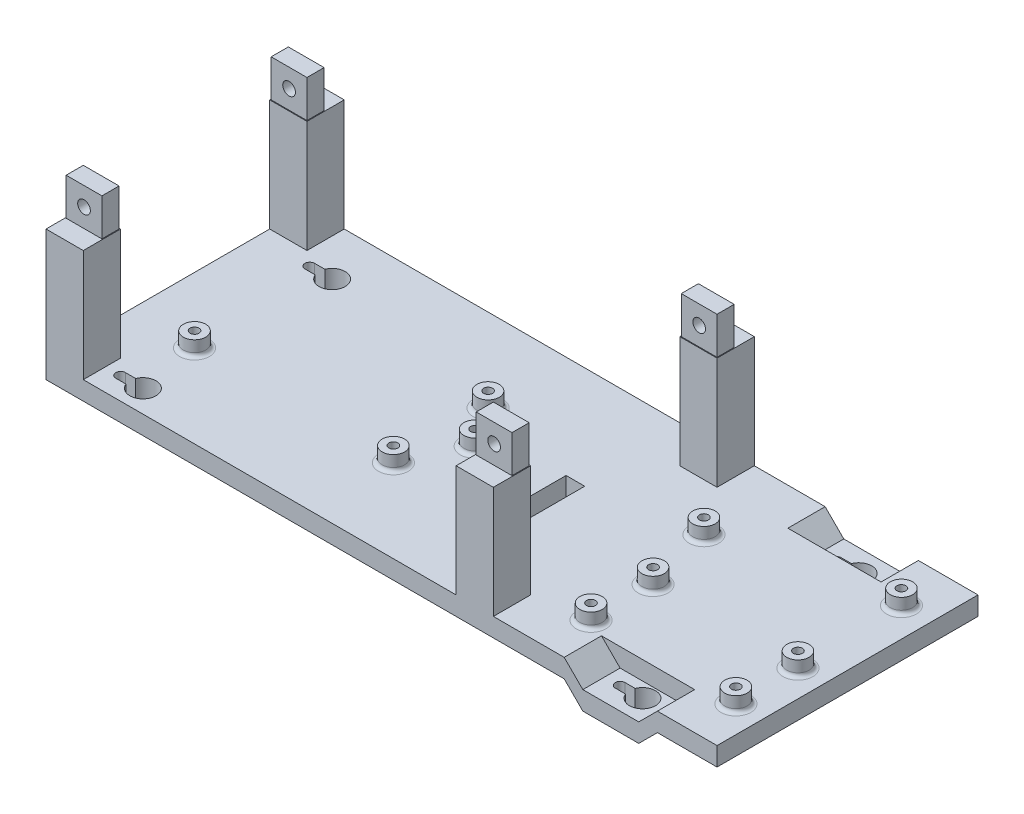
SolidWorks part; units mm, degrees
ref_plane "Front Plane" through (0, 0, 0) normal (0, 0, 1) x (1, 0, 0)
ref_plane "Top Plane" through (0, 0, 0) normal (0, 1, 0) x (1, 0, 0)
ref_plane "Right Plane" through (0, 0, 0) normal (1, 0, 0) x (0, 0, -1)
sketch "Sketch1" plane through (0, 0, 0) normal (0, 1, 0) x (1, 0, 0)
  line L1 (-90, -35) -> (90, -35)
  line L2 (-90, -35) -> (-90, 35)
  line L3 (-90, 35) -> (90, 35)
  line L4 (90, -35) -> (90, 35)
  line L5 (-90, -35) -> (90, 35) construction
  line L6 (-90, 35) -> (90, -35) construction
  point P0 (0, 0)
  dimension "D1" = 180
  dimension "D2" = 70
extrude "Boss-Extrude1" add sketch "Sketch1" along normal blind 5
sketch "Sketch3" plane through (0, 5, 0) normal (0, 1, 0) x (1, 0, 0)
  line L0 (90, 35) -> (-90, 35) construction
  line L1 (69, 35) -> (54, 35)
  line L2 (69, 35) -> (69, 25)
  line L3 (69, 25) -> (54, 25)
  line L4 (54, 35) -> (54, 25)
  line L5 (-90, -35) -> (90, -35) construction
  line L6 (69, -35) -> (54, -35)
  line L7 (69, -35) -> (69, -25)
  line L8 (69, -25) -> (54, -25)
  line L9 (54, -35) -> (54, -25)
  line L10 (90, -35) -> (90, 35) construction
  dimension "D1" = 10
  dimension "D2" = 15
  dimension "D3" = 21
extrude "Cut-Extrude1" cut sketch "Sketch3" against normal blind 6
chamfer "Chamfer2" distance 5 angle 45 4 edges at (54, 5, 30) (69, 5, 30) (69, 5, -30) (54, 5, -30)
sketch "Sketch5" plane through (0, 0, 0) normal (0, -1, 0) x (1, 0, 0)
  line L0 (-90, 35) -> (54, 35) construction
  line L1 (49, 35) -> (74, 35)
  line L2 (49, 35) -> (49, 23)
  line L3 (49, 23) -> (74, 23)
  line L4 (74, 35) -> (74, 23)
  line L5 (54, -35) -> (-90, -35) construction
  line L6 (49, -35) -> (74, -35)
  line L7 (49, -35) -> (49, -23)
  line L8 (49, -23) -> (74, -23)
  line L9 (74, -35) -> (74, -23)
  line L10 (74, 25) -> (74, 35) construction
  line L11 (49, 35) -> (49, 25) construction
  dimension "D1" = 12
extrude "Boss-Extrude7" add sketch "Sketch5" along normal blind 5
chamfer "Chamfer4" distance 5 angle 45 4 edges at (49, -5, 29) (74, -5, 29) (74, -5, -29) (49, -5, -29)
sketch "Sketch6" plane through (0, 0, 0) normal (0, 1, 0) x (1, 0, 0)
  line L0 (58, -29) -> (64, -29) construction
  line L1 (58, -27.7) -> (64, -27.7)
  line L2 (58, -30.3) -> (64, -30.3)
  line L3 (69, -35) -> (54, -35) construction
  line L5 (58, 29) -> (64, 29) construction
  line L6 (58, 30.3) -> (64, 30.3)
  line L7 (58, 27.7) -> (64, 27.7)
  line L8 (54, 35) -> (69, 35) construction
  line L9 (69, -25) -> (69, -35) construction
  circle A0 centre (64, -29) radius 3.5
  arc A1 (58, -27.7) -> (58, -30.3) centre (58, -29) ccw
  arc A2 (64, -30.3) -> (64, -27.7) centre (64, -29) ccw
  circle A3 centre (64, 29) radius 3.5
  arc A4 (58, 30.3) -> (58, 27.7) centre (58, 29) ccw
  arc A5 (64, 27.7) -> (64, 30.3) centre (64, 29) ccw
  point P2 (61, -29)
  point P15 (61, 29)
  dimension "D1" = 7
  dimension "D2" = 2.6
  dimension "D3" = 6
  dimension "D4" = 5
  dimension "D5" = 6
  dimension "D6" = 6
extrude "Cut-Extrude2" cut sketch "Sketch6" against normal through all contours A4 L6 A0 L7 | L6 A4 L7 A0 | L7 A5 L6 A0 | L1 A1 L2 | L2 A2 L1 | A2 L2 A0 L1 region at (58.7697, 0, 29) region at (64.6436, 0, 25.6587) region at (62.8105, 0, 29) region at (58.7697, 0, -29) region at (64.6436, 0, -32.3413) region at (62.8105, 0, -29)
sketch "Sketch7" plane through (0, 5, 0) normal (0, 1, 0) x (1, 0, 0)
  line L0 (-76, -29) -> (-70, -29) construction
  line L1 (-76, -27.7) -> (-70, -27.7)
  line L2 (-76, -30.3) -> (-70, -30.3)
  line L4 (-90, -35) -> (49, -35) construction
  line L5 (-90, 35) -> (-90, -35) construction
  line L6 (-76, 21.75) -> (-70, 21.75) construction
  line L7 (-76, 23.05) -> (-70, 23.05)
  line L8 (-76, 20.45) -> (-70, 20.45)
  circle A0 centre (-70, -29) radius 3.5
  arc A1 (-76, -27.7) -> (-76, -30.3) centre (-76, -29) ccw
  arc A2 (-70, -30.3) -> (-70, -27.7) centre (-70, -29) ccw
  circle A3 centre (-70, 21.75) radius 3.5
  arc A4 (-76, 23.05) -> (-76, 20.45) centre (-76, 21.75) ccw
  arc A5 (-70, 20.45) -> (-70, 23.05) centre (-70, 21.75) ccw
  point P3 (-73, -29)
  point P14 (-73, 21.75)
  dimension "D3" = 7
  dimension "D6" = 50.75
  dimension "D1" = 6
  dimension "D2" = 2.6
  dimension "D4" = 6
  dimension "D5" = 20
extrude "Cut-Extrude3" cut sketch "Sketch7" against normal through all contours A2 L2 A0 L1 | A5 L8 A3 L7 | L1 A2 L2 A1 | L8 A5 L7 A4 region at (-69.3564, 5, 25.6587) region at (-69.3564, 5, -25.0913)
sketch "Sketch8" plane through (0, 5, 0) normal (0, 1, 0) x (1, 0, 0)
  line L1 (-90, -35) -> (-80, -35)
  line L2 (-90, -35) -> (-90, -25)
  line L3 (-90, -25) -> (-80, -25)
  line L4 (-80, -35) -> (-80, -25)
  line L5 (-90, 35) -> (-80, 35)
  line L6 (-90, 35) -> (-90, 25)
  line L7 (-90, 25) -> (-80, 25)
  line L8 (-80, 35) -> (-80, 25)
  line L9 (30, -35) -> (20, -35)
  line L10 (30, -35) -> (30, -25)
  line L11 (30, -25) -> (20, -25)
  line L12 (20, -35) -> (20, -25)
  line L13 (30, 35) -> (20, 35)
  line L14 (30, 35) -> (30, 25)
  line L15 (30, 25) -> (20, 25)
  line L16 (20, 35) -> (20, 25)
  dimension "D1" = 10
  dimension "D2" = 10
  dimension "D3" = 120
extrude "Boss-Extrude8" add sketch "Sketch8" along normal blind 40
sketch "Sketch9" plane through (0, 45, 0) normal (0, 1, 0) x (1, 0, 0)
  line L1 (20, 35) -> (20, 25) construction
  line L2 (30, 35) -> (20, 35)
  line L3 (30, 35) -> (30, 30)
  line L4 (30, 30) -> (20, 30)
  line L5 (20, 35) -> (20, 30)
  line L6 (-90, 35) -> (-90, 25) construction
  line L8 (-80, 35) -> (-90, 35)
  line L9 (-80, 35) -> (-80, 30)
  line L10 (-80, 30) -> (-90, 30)
  line L11 (-90, 35) -> (-90, 30)
  line L12 (-90, -25) -> (-90, -35) construction
  line L14 (-80, -35) -> (-90, -35)
  line L15 (-80, -35) -> (-80, -30)
  line L16 (-80, -30) -> (-90, -30)
  line L17 (-90, -35) -> (-90, -30)
  line L18 (20, -25) -> (20, -35) construction
  line L20 (30, -35) -> (20, -35)
  line L21 (30, -35) -> (30, -30)
  line L22 (30, -30) -> (20, -30)
  line L23 (20, -35) -> (20, -30)
  line L57 (-90, 30) -> (-89.9, 30)
  line M1 (30, 25) -> (30, 35)
  line M2 (30, 35) -> (20, 35)
  line M3 (20, 35) -> (20, 25)
extrude "Cut-Extrude4" cut sketch "Sketch9" against normal blind 10 contours L10 | L10 | L22 | L22 | L16 | L16 | L23 L20 L21 L22 | L4 M1 M2 M3 | L8 L11 L10 L9 | L17 L14 L15 L16 region at (25, 45, -32.5) region at (-85, 45, -32.5) region at (-85, 45, 32.5) region at (25, 45, 32.5)
hole_wizard "M3 Clearance Hole2" positions "Sketch13" profile "Sketch12" hole size "M3" standard "ANSI Metric" end condition through all
sketch "Sketch13" plane through (0, 0, -35) normal (0, 0, -1) x (-1, 0, 0)
  line L0 (-20, 35) -> (-20, 5) construction
  line L1 (-30, 45) -> (-20, 45) construction
  line L2 (80, 35) -> (80, 5) construction
  point P0 (-25, 40)
  point P2 (85, 40)
  dimension "D1" = 5
  dimension "D2" = 5
  dimension "D3" = 5
sketch "Sketch12" plane through (25, 40, -35) normal (1, 0, 0) x (0, 1, 0)
  line L0 (0, 0) -> (0, 70.0001)
  line L1 (0, 70.0001) -> (1.7, 70.0001)
  line L2 (1.7, 70.0001) -> (1.7, 0)
  line L5 (1.7, 0) -> (0, 0)
  line L11 (0, -6.35) -> (0, 107.95) construction
  dimension "Thru Hole Dia." = 3.4
  dimension "Thru Hole Depth" = 70.0001
hole_wizard "M2 Clearance Hole1" positions "Sketch15" profile "Sketch14" hole size "M2" standard "ANSI Metric"
sketch "Sketch15" plane through (0, 5, 0) normal (0, 1, 0) x (1, 0, 0)
  circle A0 centre (-11.9765, 2.0955) radius 1.0414 construction
  circle A1 centre (4.5335, -12.5095) radius 1.0414 construction
  circle A2 centre (43.979, -22.7775) radius 1.0922 construction
  circle A3 centre (43.979, -6.1405) radius 1.0922 construction
  circle A4 centre (82.841, -22.7775) radius 1.0922 construction
  circle A5 centre (82.841, -6.1405) radius 1.0922 construction
  circle A7 centre (39.235, 12.25) radius 1.0922 construction
  point P0 (43.979, -22.7775)
  point P2 (43.979, -6.1405)
  point P4 (82.841, -6.1405)
  point P6 (82.841, -22.7775)
  point P8 (82.1869, 22.2793)
  point P10 (39.235, 12.25)
  point P12 (4.5335, -12.5095)
  point P14 (-11.9765, 2.0955)
sketch "Sketch14" plane through (43.979, 5, 22.7775) normal (1, 0, 0) x (0, 0, 1)
  line L0 (0, 0) -> (0, 65.741)
  line L1 (0, 65.741) -> (1.2, 65.02)
  line L2 (1.2, 65.02) -> (1.2, 0)
  line L5 (1.2, 0) -> (0, 0)
  line L10 (0, 65.741) -> (-1.2, 65.02) construction
  line L11 (0, -6.35) -> (0, 107.95) construction
  dimension "Hole Dia." = 2.4
  dimension "Hole Depth" = 65.02
  dimension "Drill Angle" = 118
sketch "Sketch16" plane through (0, 45, 0) normal (0, 1, 0) x (1, 0, 0)
  line L18 (20.2, 29.8) -> (20.2, 25.2)
  line L19 (29.8, 29.8) -> (20.2, 29.8)
  line L20 (20.2, 25.2) -> (29.8, 25.2)
  line L21 (29.8, 25.2) -> (29.8, 29.8)
  line L22 (20.2, 29.8) -> (20.2, 25.2)
  line L23 (29.8, 29.8) -> (20.2, 29.8)
  line L24 (20.2, 25.2) -> (29.8, 25.2)
  line L25 (29.8, 25.2) -> (29.8, 29.8)
  line L46 (-80.2, 29.8) -> (-89.8, 29.8)
  line L47 (-89.8, 29.8) -> (-89.8, 25.2)
  line L48 (-89.8, 25.2) -> (-80.2, 25.2)
  line L49 (-80.2, 25.2) -> (-80.2, 29.8)
  line L50 (-80.2, 29.8) -> (-89.8, 29.8)
  line L51 (-89.8, 29.8) -> (-89.8, 25.2)
  line L52 (-89.8, 25.2) -> (-80.2, 25.2)
  line L53 (-80.2, 25.2) -> (-80.2, 29.8)
  line L64 (-80.2, -25.2) -> (-89.8, -25.2)
  line L65 (-89.8, -25.2) -> (-89.8, -29.8)
  line L66 (-89.8, -29.8) -> (-80.2, -29.8)
  line L67 (-80.2, -29.8) -> (-80.2, -25.2)
  line L68 (-80.2, -25.2) -> (-89.8, -25.2)
  line L69 (-89.8, -25.2) -> (-89.8, -29.8)
  line L70 (-89.8, -29.8) -> (-80.2, -29.8)
  line L71 (-80.2, -29.8) -> (-80.2, -25.2)
  line L117 (20.2, -25.2) -> (20.2, -29.8)
  line L118 (20.2, -29.8) -> (29.8, -29.8)
  line L119 (29.8, -29.8) -> (29.8, -25.2)
  line L120 (29.8, -25.2) -> (20.2, -25.2)
  line L121 (20.2, -25.2) -> (20.2, -29.8)
  line L122 (20.2, -29.8) -> (29.8, -29.8)
  line L123 (29.8, -29.8) -> (29.8, -25.2)
  line L124 (29.8, -25.2) -> (20.2, -25.2)
  dimension "D1" = 0.2
  dimension "D2" = 0.2
  dimension "D3" = 0.2
  dimension "D4" = 0.2
extrude "Cut-Extrude5" cut sketch "Sketch16" against normal blind 10 flip side to cut
hole_wizard "M2 Clearance Hole2" positions "Sketch21" profile "Sketch20" hole size "M2" standard "ANSI Metric" end condition through all
sketch "Sketch21" plane through (0, 5, 0) normal (0, 1, 0) x (1, 0, 0)
  circle A0 centre (-19.12, -12.7) radius 1.0922 construction
  circle A1 centre (-19.12, 12.7) radius 1.0922 construction
  circle A2 centre (-72.46, -12.7) radius 1.0922 construction
  point P0 (-19.12, 12.7)
  point P2 (-19.12, -12.7)
  point P4 (-72.46, -12.7)
sketch "Sketch20" plane through (-19.12, 5, -12.7) normal (1, 0, 0) x (0, 0, 1)
  line L0 (0, 0) -> (0, 10)
  line L1 (0, 10) -> (1.2, 10)
  line L2 (1.2, 10) -> (1.2, 0)
  line L5 (1.2, 0) -> (0, 0)
  line L11 (0, -6.35) -> (0, 107.95) construction
  dimension "Thru Hole Dia." = 2.4
  dimension "Thru Hole Depth" = 10
sketch "Sketch17" plane through (0, 5, 0) normal (0, 1, 0) x (1, 0, 0)
  circle A0 centre (-19.12, 12.7) radius 3
  circle A1 centre (82.1869, 22.2793) radius 3
  circle A2 centre (-19.12, -12.7) radius 3
  circle A3 centre (39.235, 12.25) radius 3
  circle A4 centre (-72.46, -12.7) radius 3
  circle A5 centre (43.979, -6.1405) radius 3
  circle A7 centre (43.979, -22.7775) radius 3
  circle A9 centre (82.841, -22.7775) radius 3
  circle A11 centre (82.841, -6.1405) radius 3
  circle A13 centre (4.5335, -12.5095) radius 3
  circle A15 centre (-11.9765, 2.0955) radius 3
  circle M1 centre (43.979, -6.1405) radius 1.2
  circle M2 centre (82.1869, 22.2793) radius 1.2
  circle M3 centre (39.235, 12.25) radius 1.2
  circle M4 centre (4.5335, -12.5095) radius 1.2
  circle M5 centre (-11.9765, 2.0955) radius 1.2
  line M25 (20, -25) -> (30, -25)
  circle M38 centre (82.841, -22.7775) radius 1.2
  circle M39 centre (82.841, -6.1405) radius 1.2
  circle M40 centre (43.979, -22.7775) radius 1.2
  circle M49 centre (-19.12, 12.7) radius 1.2
  circle M50 centre (-72.46, -12.7) radius 1.2
  circle M51 centre (-19.12, -12.7) radius 1.2
  dimension "D1" = 6
extrude "Boss-Extrude9" add sketch "Sketch17" along normal blind 4 contours A1 M2 | A11 M39 | A9 M38 | A7 M40 | A5 M1 | A3 M3 | A13 M25 M4 | A15 M5 | A0 M49 | A2 M51 | A4 M50 region at (-22.0351, 5, -12.7) region at (79.2717, 5, -22.2793) region at (-22.0351, 5, 12.7) region at (36.3199, 5, -12.25) region at (-75.3751, 5, 12.7) region at (41.0639, 5, 6.1405) region at (41.0639, 5, 22.7775) region at (79.9259, 5, 22.7775) region at (79.9259, 5, 6.1405) region at (1.6184, 5, 12.5095) region at (-14.8916, 5, -2.0955)
sketch "Sketch22" plane through (0, 5, 0) normal (0, 1, 0) x (1, 0, 0)
  line L0 (12.01, 7.5) -> (7.01, 7.5)
  line L1 (12.01, 7.5) -> (12.01, -7.5)
  line L2 (7.01, 7.5) -> (7.01, -7.5)
  line L3 (12.01, -7.5) -> (7.01, -7.5)
  line L4 (12.01, 7.5) -> (7.01, -7.5) construction
  line L5 (7.01, 7.5) -> (12.01, -7.5) construction
  line L6 (7.01, -15.24) -> (7.01, 15.24) construction
  line L7 (90, 0) -> (-90, 0) construction
  line L8 (90, -35) -> (90, 35) construction
  line L9 (-90, 25) -> (-90, -25) construction
  point P1 (9.51, 0)
  dimension "D1" = 5
  dimension "D2" = 15
extrude "Cut-Extrude6" cut sketch "Sketch22" against normal through all
fillet "Fillet1" radius 1 11 edges at (-72.46, 5, 9.7) (-19.12, 5, 9.7) (-19.12, 5, -15.7) (-11.9765, 5, -5.0955) (4.5335, 5, 9.5095) (39.235, 5, -15.25) (43.979, 5, 3.1405) (43.979, 5, 19.7775) (82.841, 5, 19.7775) (82.841, 5, 3.1405) (82.1869, 5, -25.2793)
equation "\"D6@Sketch6\"=\"D3@Sketch6\""
equation "\"D3@Sketch13\"=\"D1@Sketch13\""
equation "\"D2@Sketch16\"=\"D1@Sketch16\""
equation "\"D3@Sketch16\"=\"D1@Sketch16\""
equation "\"D4@Sketch16\"=\"D1@Sketch16\""
